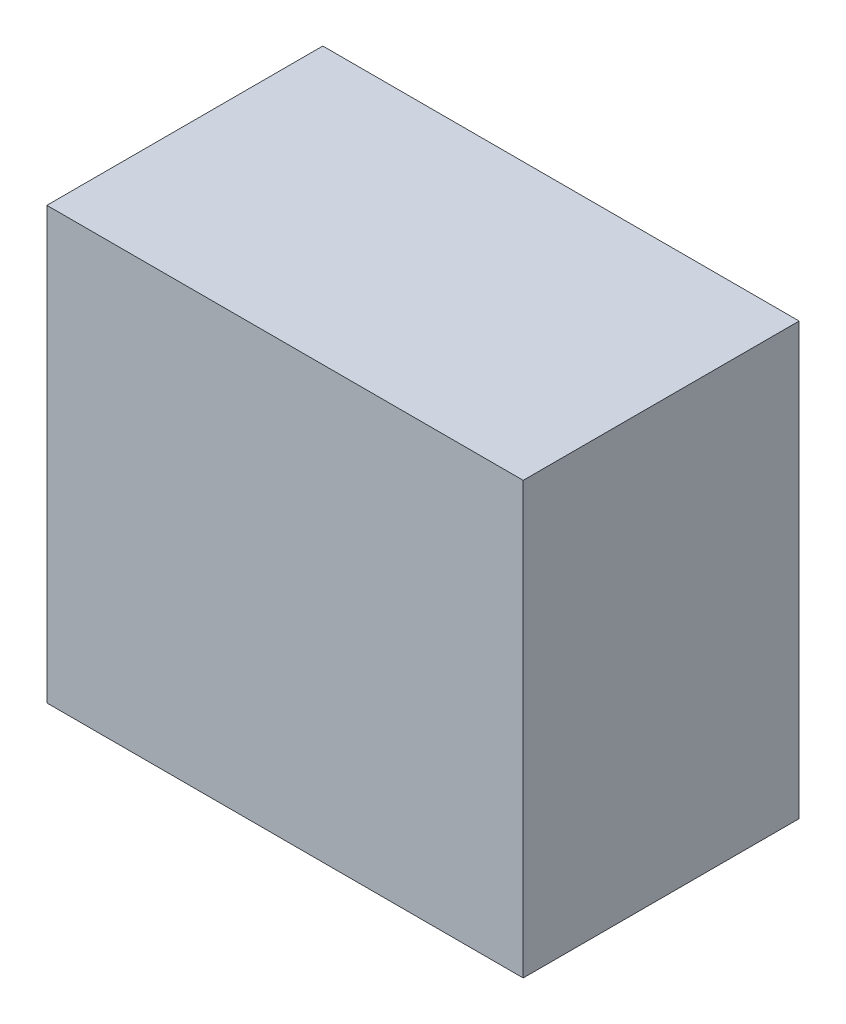
SolidWorks part; units mm, degrees
material "1060 Alloy"
ref_plane "Front" through (0, 0, 0) normal (0, 0, 1) x (1, 0, 0)
ref_plane "Top" through (0, 0, 0) normal (0, 1, 0) x (1, 0, 0)
ref_plane "Right" through (0, 0, 0) normal (1, 0, 0) x (0, 0, -1)
sketch "Sketch3" plane through (0, 0, 0) normal (0, 0, 1) x (1, 0, 0)
  line L0 (-0.127, -6.35) -> (30.1755, -6.35)
  line L1 (0, 0) -> (21.9242, 0)
  line L2 (0, 0) -> (0, -19.8376)
  line L3 (0, -19.8376) -> (21.9242, -19.8376)
  line L4 (21.9242, 0) -> (21.9242, -19.8376)
  line L5 (15.5742, -19.8376) -> (15.5742, 0) construction
  line L6 (15.5742, -6.35) -> (8.0621, -19.3614) construction
  line L15 (12.5496, -11.5887) -> (15.5742, -13.335) construction
  circle A0 centre (15.5742, -6.35) radius 6.0492 construction
  point P14 (0, -6.35)
  point P17 (9.525, -6.35)
  point P20 (7.7871, -19.8376)
  dimension "D2" = 6.35
  dimension "D6" = 3.4925
  dimension "D3" = 60
  dimension "D1" = 9.525
  dimension "D4" = 9.525
  dimension "D5" = 6.35
extrude "Boss-Extrude1" add sketch "Sketch3" along normal mid plane 12.7
sketch "Sketch4" plane through (0, 0, 0) normal (-1, 0, 0) x (0, 0, 1)
  circle A0 centre (0, -6.35) radius 3.175
  dimension "D1" = 6.35
extrude "Cut-Extrude1" cut sketch "Sketch4" against normal blind 9.525
ref_plane "Plane1" through (7.7871, -19.8376, 0) normal (-0.5, -0.866, 0) x (-0.866, 0.5, 0)
ref_plane "Mirror Plane" through (15.5742, 0, 0) normal (-1, 0, 0) x (0, 0, 1)
sketch "Sketch5" plane through (7.7871, -19.8376, 0) normal (-0.5, -0.866, 0) x (-0.866, 0.5, 0)
  circle A0 centre (0, 0) radius 3.175
  dimension "D1" = 6.35
extrude "Cut-Extrude5" cut sketch "Sketch5" against normal blind 9.525 and the other way up to next
sketch "Sketch6" plane through (0, 0, -6.35) normal (0, 0, -1) x (-1, 0, 0)
  circle A0 centre (-15.5742, -6.35) radius 3.175
  dimension "D1" = 6.35
extrude "Cut-Extrude6" cut sketch "Sketch6" against normal blind 9.525
equation "\"truss_member_od\" = .25in"
equation "\"truss_member_id\"= 0in"
equation "\"truss_member_L1\" = 2.125in"
equation "\"connector_hole_depth\" = .375in"
equation "\"D1@Boss-Extrude1\"=\"truss_member_od\"*2"
equation "\"D6@Sketch3\"=\"truss_member_od\"/2*1.1"
equation "\"D1@Sketch4\"=\"truss_member_od\""
equation "\"D1@Cut-Extrude1\"=\"connector_hole_depth\""
equation "\"D1@Sketch3\"=\"connector_hole_depth\""
equation "\"D4@Sketch3\"=\"connector_hole_depth\""
equation "\"D1@Sketch5\"=\"truss_member_od\""
equation "\"D1@Cut-Extrude5\"=\"connector_hole_depth\""
equation "\"D1@Cut-Extrude6\"=\"connector_hole_depth\""
equation "\"D1@Sketch6\"=\"truss_member_od\""
equation "\"D5@Sketch3\"=\"truss_member_od\""
